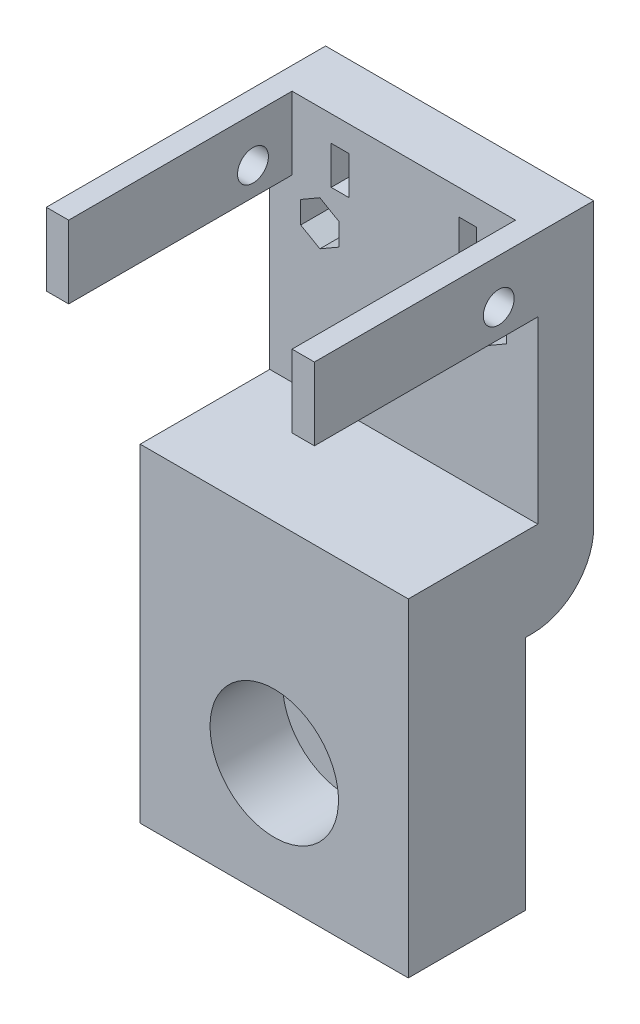
SolidWorks part; units mm, degrees
ref_plane "Front Plane" through (0, 0, 0) normal (0, 0, 1) x (1, 0, 0)
ref_plane "Top Plane" through (0, 0, 0) normal (0, 1, 0) x (1, 0, 0)
ref_plane "Right Plane" through (0, 0, 0) normal (1, 0, 0) x (0, 0, -1)
sketch "Sketch1" plane through (0, 0, 0) normal (0, 0, 1) x (1, 0, 0)
  line L1 (0, 0) -> (48, 0)
  line L2 (0, 0) -> (0, 53)
  line L3 (0, 53) -> (48, 53)
  line L4 (48, 0) -> (48, 53)
  circle A0 centre (8.975, 38) radius 1.9304
  circle A1 centre (38.975, 38) radius 1.9304
  dimension "D1" = 53
  dimension "D2" = 48
extrude "Boss-Extrude1" add sketch "Sketch1" along normal blind 10
sketch "Sketch2" plane through (0, 0, 0) normal (0, 0, -1) x (-1, 0, 0)
  line L0 (0, 53) -> (0, 0) construction
  line L1 (-48, 0) -> (0, 0)
  line L2 (-48, 0) -> (-48, -5.6163)
  line L3 (-48, -5.6163) -> (0, -5.6163)
  line L4 (0, 0) -> (0, -5.6163)
  dimension "D1" = 5.6163
extrude "Boss-Extrude2" add sketch "Sketch2" against normal blind 33.1918
sketch "Sketch4" plane through (0, 0, 10) normal (0, 0, 1) x (1, 0, 0)
  line L1 (0, 53) -> (4, 53)
  line L2 (0, 53) -> (0, 43)
  line L3 (0, 43) -> (4, 43)
  line L4 (4, 53) -> (4, 43)
  line L5 (48, 53) -> (44, 53)
  line L6 (48, 53) -> (48, 43)
  line L7 (48, 43) -> (44, 43)
  line L8 (44, 53) -> (44, 43)
  dimension "D1" = 10
  dimension "D2" = 4
extrude "Boss-Extrude4" add sketch "Sketch4" along normal blind 40
sketch "Sketch5" plane through (0, 0, 10) normal (0, 0, 1) x (1, 0, 0)
  line L0 (48, 0) -> (48, 43) construction
  line L1 (0, 0) -> (48, 0)
  line L2 (0, 0) -> (0, 10.8609)
  line L3 (0, 10.8609) -> (48, 10.8609)
  line L4 (48, 0) -> (48, 10.8609)
  dimension "D1" = 10.8609
extrude "Boss-Extrude5" add sketch "Sketch5" along normal up to surface (23.1918 mm away) up to face at (24, -2.8082, 33.1918)
sketch "Sketch6" plane through (0, -5.6163, 0) normal (0, -1, 0) x (1, 0, 0)
  line L0 (0, 0) -> (0, 28.1918) construction
  line L1 (0, 33.1918) -> (0, 0) construction
  line L2 (48, 33.1918) -> (48, 0) construction
  line L3 (0, 28.1918) -> (48, 28.1918)
  line L4 (0, 28.1918) -> (0, 33.1918)
  line L5 (0, 33.1918) -> (48, 33.1918)
  line L6 (48, 28.1918) -> (48, 33.1918)
  line L8 (48, 33.1918) -> (0, 33.1918) construction
  dimension "D2" = 5
extrude "Boss-Extrude6" add sketch "Sketch6" along normal blind 42.3
sketch "Sketch8" plane through (0, 0, 28.1918) normal (0, 0, -1) x (-1, 0, 0)
  line L0 (-24, -26.6163) -> (-24, -5.6163) construction
  line L1 (0, -5.6163) -> (-48, -5.6163) construction
  line L3 (-8.5, -42.1163) -> (-39.5, -42.1163) construction
  line L4 (-8.5, -42.1163) -> (-8.5, -11.1163) construction
  line L5 (-8.5, -11.1163) -> (-39.5, -11.1163) construction
  line L6 (-39.5, -42.1163) -> (-39.5, -11.1163) construction
  line L7 (-8.5, -42.1163) -> (-39.5, -11.1163) construction
  line L8 (-8.5, -11.1163) -> (-39.5, -42.1163) construction
  circle A0 centre (-24, -26.6163) radius 11.5
  circle A1 centre (-39.5, -11.1163) radius 2 construction
  circle A2 centre (-39.5, -42.1163) radius 2 construction
  circle A3 centre (-8.5, -11.1163) radius 2 construction
  circle A4 centre (-8.5, -42.1163) radius 2 construction
  dimension "D2" = 23
  dimension "D4" = 4
  dimension "D1" = 21
  dimension "D3" = 31
extrude "Cut-Extrude1" cut sketch "Sketch8" against normal up to next
sketch "Sketch9" plane through (48, 0, 0) normal (1, 0, 0) x (0, 0, -1)
  line L0 (0, -5.6163) -> (0, 53) construction
  line L1 (-50, 43) -> (-17, 48) construction
  line L2 (-17, 48) -> (-50, 53) construction
  circle A0 centre (-17, 48) radius 2.7623
  dimension "D1" = 5.5245
  dimension "D2" = 17
extrude "Cut-Extrude2" cut sketch "Sketch9" against normal through all
sketch "Sketch10" plane through (0, 0, 0) normal (0, 0, -1) x (-1, 0, 0)
  line L0 (-48, 53) -> (-37, 51.4163) construction
  line L1 (-37, 51.4163) -> (-33.8453, 51.4163)
  line L2 (-37, 51.4163) -> (-37, 44.5837)
  line L3 (-37, 44.5837) -> (-33.8453, 44.5837)
  line L4 (-33.8453, 51.4163) -> (-33.8453, 44.5837)
  line L5 (-14.1547, 51.4163) -> (-11, 51.4163)
  line L6 (-14.1547, 51.4163) -> (-14.1547, 44.5837)
  line L7 (-14.1547, 44.5837) -> (-11, 44.5837)
  line L8 (-11, 51.4163) -> (-11, 44.5837)
  line L9 (0, 53) -> (-11, 51.4163) construction
  line L10 (-48, 53) -> (0, 53) construction
  dimension "D1" = 3.1547
  dimension "D2" = 1.5837
  dimension "D3" = 6.8326
  dimension "D4" = 19.6906
extrude "Cut-Extrude3" cut sketch "Sketch10" against normal up to next
sketch "Sketch11" plane through (0, 0, 28.1918) normal (0, 0, -1) x (-1, 0, 0)
  line L1 (-48, -5.6163) -> (0, -5.6163)
  line L2 (-48, -5.6163) -> (-48, -47.9163)
  line L3 (-48, -47.9163) -> (0, -47.9163)
  line L4 (0, -5.6163) -> (0, -47.9163)
  circle A0 centre (-24, -26.6163) radius 11.5
  circle A1 centre (-24, -26.6163) radius 11.5 construction
extrude "Boss-Extrude7" add sketch "Sketch11" along normal blind 8
sketch "Sketch12" plane through (0, 0, 20.1918) normal (0, 0, -1) x (-1, 0, 0)
  line L1 (-48, -5.6163) -> (0, -5.6163)
  line L2 (-48, -5.6163) -> (-48, -47.9163)
  line L3 (-48, -47.9163) -> (0, -47.9163)
  line L4 (0, -5.6163) -> (0, -47.9163)
extrude "Boss-Extrude8" add sketch "Sketch12" along normal blind 8
fillet "Fillet1" radius 11 1 edges at (24, -5.6163, 0)
sketch "Sketch13" plane through (0, 53, 0) normal (0, 1, 0) x (1, 0, 0)
  line L0 (0, 0) -> (0, -50)
  line L1 (0, -50) -> (4, -50)
  line L2 (4, -50) -> (4, -10)
  line L3 (4, -10) -> (44, -10)
  line L4 (44, -10) -> (44, -50)
  line L5 (44, -50) -> (48, -50)
  line L6 (48, -50) -> (48, 0)
  line L7 (48, 0) -> (0, 0)
extrude "Boss-Extrude9" add sketch "Sketch13" along normal blind 3
sketch "Sketch14" plane through (0, 0, 10) normal (0, 0, 1) x (1, 0, 0)
  line L1 (8.975, 41.9595) -> (5.546, 39.9797)
  line L2 (5.546, 39.9797) -> (5.546, 36.0203)
  line L3 (5.546, 36.0203) -> (8.975, 34.0405)
  line L4 (8.975, 34.0405) -> (12.404, 36.0203)
  line L5 (12.404, 36.0203) -> (12.404, 39.9797)
  line L6 (12.404, 39.9797) -> (8.975, 41.9595)
  line L7 (38.975, 41.9595) -> (35.546, 39.9797)
  line L8 (35.546, 39.9797) -> (35.546, 36.0203)
  line L9 (35.546, 36.0203) -> (38.975, 34.0405)
  line L10 (38.975, 34.0405) -> (42.404, 36.0203)
  line L11 (42.404, 36.0203) -> (42.404, 39.9797)
  line L12 (42.404, 39.9797) -> (38.975, 41.9595)
  circle A0 centre (8.975, 38) radius 3.429 construction
  circle A1 centre (38.975, 38) radius 3.429 construction
  dimension "D1" = 3.9595
extrude "Cut-Extrude4" cut sketch "Sketch14" against normal blind 6
